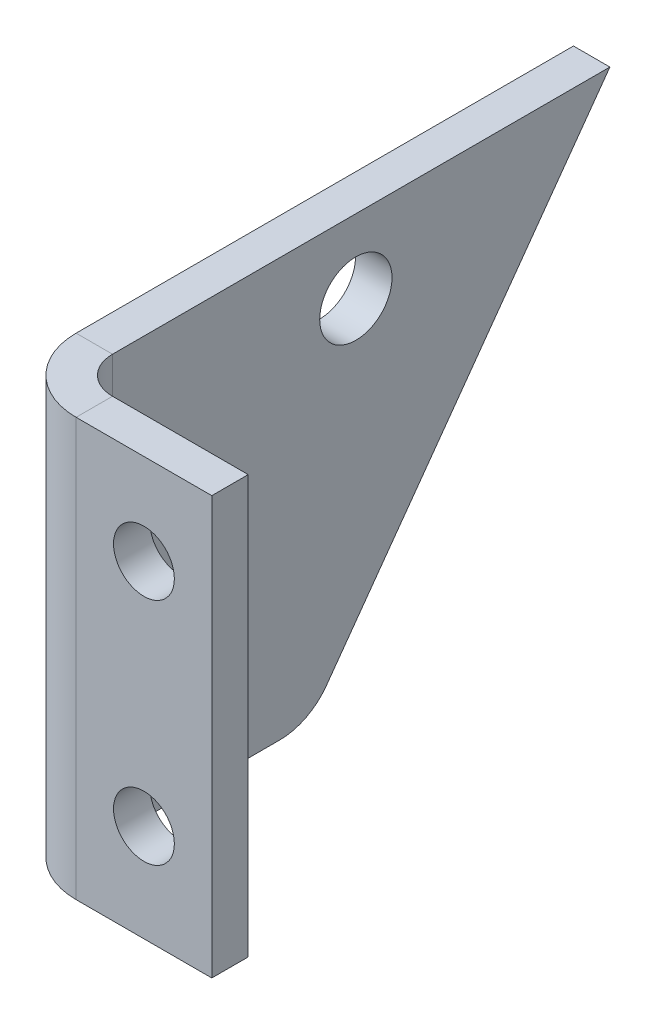
SolidWorks part; units mm, degrees
note: The reader was unsure of these and kept them because the rebuilt part matched: flange length of "Edge-Flange1".
ref_plane "Front Plane" through (0, 0, 0) normal (0, 0, 1) x (1, 0, 0)
ref_plane "Top Plane" through (0, 0, 0) normal (0, 1, 0) x (1, 0, 0)
ref_plane "Right Plane" through (0, 0, 0) normal (1, 0, 0) x (0, 0, -1)
sketch "Sketch1" plane through (0, 0, 0) normal (1, 0, 0) x (0, 0, -1)
  line B0 (15.5145, 80.4634) -> (48.2755, 80.6063)
  line B1 (53.2972, 75.6298) -> (53.4491, 43.2583)
  line B2 (0, 0) -> (0, 38.4283)
  line B3 (0, 38.4283) -> (-38.5, 38.5)
  line B4 (-38.5, 38.5) -> (-38.5, 49.4616)
  line B5 (-35.8424, 53.8789) -> (13.1939, 79.8808)
  line B6 (0, 0) -> (20.9311, 0)
  line B7 (24.9893, 2.0792) -> (52.5074, 40.3141)
  arc B8 (53.2972, 75.6298) -> (48.2755, 80.6063) centre (48.2973, 75.6063) ccw
  arc B9 (-38.5, 49.4616) -> (-35.8424, 53.8789) centre (-33.5, 49.4616) cw
  arc B10 (20.9311, 0) -> (24.9893, 2.0792) centre (20.9311, 5) ccw
  circle B11 centre (16.9387, 43.9655) radius 1.5
  ellipse B12 centre (47.9374, 44.1038) end of major axis (47.1974, 45.4086) minor radius 1.5
  spline B13 degree 3 poles (27.4588, 48.3261) (32.0962, 47.4253) (36.7252, 48.3676) (40.6413, 51.0097) (43.2482, 54.9493) (44.149, 59.5866) (43.2066, 64.2157) (40.5646, 68.1317) (36.625, 70.7386) (31.9877, 71.6394) (27.3586, 70.6971) (23.4426, 68.055) (20.8357, 64.1154) (19.9348, 59.4781) (20.8772, 54.8491) (23.5193, 50.933) (27.4588, 48.3261) (32.0962, 47.4253) (36.7252, 48.3676) knots -1.178097 -0.785398 -0.392699 0 0.392699 0.785398 1.178097 1.570796 1.963495 2.356194 2.748894 3.141593 3.534292 3.926991 4.31969 4.712389 5.105088 5.497787 5.890486 6.283185 6.675884 7.068583 7.461283 only from (32.0948, 47.7325) to (32.0948, 47.7325)
sketch_block_instance "motormount-1"
sketch_block "motormount" parameters "D1"=5
sketch "Sketch2" plane through (0, 0, 0) normal (1, 0, 0) x (0, 0, -1)
  line L0 (0, 0) -> (0, 38.4283) construction
  line L1 (0, 0) -> (20.9311, 0) construction
  line L2 (24.9893, 2.0792) -> (52.5074, 40.3141) construction
  line L3 (0, 0) -> (0, 36.404)
  line L4 (0, 0) -> (20.9311, 0)
  line L5 (24.9893, 2.0792) -> (49.6932, 36.404)
  line L6 (0, 36.404) -> (49.6932, 36.404)
  arc A0 (20.9311, 0) -> (24.9893, 2.0792) centre (20.9311, 5) ccw construction
  arc A1 (20.9311, 0) -> (24.9893, 2.0792) centre (20.9311, 5) ccw
base flange "Base-Flange1" sketch "Sketch2" thickness 3.175 reverse thickness direction no parameters "D1"=3.175
sketch "Sketch7" plane through (-3.175, 0, 0) normal (-1, 0, 0) x (0, 0, 1)
  line L0 (0, 0) -> (0, 10) construction
  line L1 (0, 0) -> (0, 38.4283) construction
  line L2 (-12.5877, 6.85) -> (-12.5877, 13.15) construction
  line L3 (0, 10) -> (0, 30.7947) construction
  line L4 (-26.1531, 27.1786) -> (-28.9547, 32.8214) construction
  line L5 (0, 10) -> (-30.69, 10)
  line L6 (-24.9893, 2.0792) -> (-52.5074, 40.3141) construction
  line L10 (-24.9893, 2.0792) -> (-49.6932, 36.404) construction
  line L11 (-24.9893, 2.0792) -> (-49.6932, 36.404)
  circle A0 centre (-27.5539, 30) radius 3.15
  circle A1 centre (-12.5877, 10) radius 3.15
  point P9 (-12.5877, 10)
  point P15 (-22.5421, 30)
  dimension "D3" = 6.3
  dimension "D4" = 6.3
  dimension "D1" = 10
  dimension "D2" = 20
extrude "Cut-Extrude3" cut sketch "Sketch7" against normal blind 10 contours A0 | A1 normal cut yes
edge flange "Edge-Flange1" sketch "Sketch11" flange angle 90 flange length 15 flange position material inside bend radius 3.175 thickness 3.175 relief rectangular parameters "D6"=10
sketch "Sketch11" plane through (0, 0, 0) normal (0, 0, -1) x (0, 1, 0)
  line L0 (36.404, 0) -> (0, 0) construction
  line L2 (0, 0) -> (0, 15)
  line L3 (0, 15) -> (36.404, 15)
  line L4 (36.404, 15) -> (36.404, 0)
  line L5 (36.404, 0) -> (0, 0)
bend "EdgeBend1" bend radius 3.175 bend angle 90 parameters "D5"=1
sketch "Sketch12" plane through (0, 0, -3.175) normal (0, 0, -1) x (-1, 0, 0)
  line L0 (-9.0875, 36.404) -> (-9.0875, -2.0794) construction
  line L1 (-3.175, 36.404) -> (-15, 36.404) construction
  circle A0 centre (-9.0875, 28.4964) radius 2.65
  circle A1 centre (-9.0875, 8.4966) radius 2.65
  line B0 (-29.9951, 80.363) -> (-29.9958, 74.363)
  line B1 (-29.9958, 74.363) -> (-9.9958, 74.3607)
  line B2 (-9.9958, 74.3607) -> (-9.9951, 80.3607)
  line B3 (-9.9951, 80.3607) -> (-29.9951, 80.363)
  line B4 (-39.9997, 41.3642) -> (-40, 38.3642)
  line B5 (-40, 38.3642) -> (-30, 38.363)
  line B6 (-30, 38.363) -> (-29.9997, 41.363)
  line B7 (-10, 38.3607) -> (0, 38.3596)
  line B8 (0, 38.3596) -> (0.0003, 41.3596)
  line B9 (-9.9997, 41.3607) -> (-10, 38.3607)
  line B10 (-29.9993, 44.363) -> (-30, 38.363)
  line B11 (-30, 38.363) -> (-10, 38.3607)
  line B12 (-10, 38.3607) -> (-9.9993, 44.3607)
  line B13 (0.0003, 41.3596) -> (0.0045, 77.3596)
  line B14 (-9.9955, 77.3607) -> (-9.9958, 74.3607)
  line B15 (-9.9958, 74.3607) -> (-29.9958, 74.363)
  line B16 (-29.9958, 74.363) -> (-29.9955, 77.363)
  line B17 (-39.9955, 77.3642) -> (-39.9997, 41.3642)
  line B18 (-29.9997, 41.363) -> (-29.9993, 44.363)
  line B19 (-9.9993, 44.3607) -> (-9.9997, 41.3607)
  line B20 (-29.9951, 80.363) -> (-39.9951, 80.3642)
  line B21 (-39.9951, 80.3642) -> (-39.9955, 77.3642)
  line B22 (-29.9955, 77.363) -> (-29.9951, 80.363)
  line B23 (0.0045, 77.3596) -> (0.0049, 80.3596)
  line B24 (0.0049, 80.3596) -> (-9.9951, 80.3607)
  line B25 (-9.9951, 80.3607) -> (-9.9955, 77.3607)
  line B26 (380.7227, 28.4513) -> (-19.2773, 28.4976)
  line B27 (380.7203, 8.4515) -> (-19.2797, 8.4978)
  line B28 (380.7194, -0.0771) -> (-19.2806, -0.0308)
  line B29 (380.7236, 36.9226) -> (-19.2764, 36.9688)
  dimension "D1" = 5.3
  dimension "D2" = 5.3
sketch_block_instance "motormount_back-1"
sketch_block "motormount_back" parameters "D1"=5.4262, "D2"=5.7071
extrude "Cut-Extrude4" cut sketch "Sketch12" against normal blind 10 contours L0 A0 B26 | A0 L0 B26 | A1
sketch "Bend-Lines1" [suppressed] plane through (0, 0, 0) normal (0, 1, 0) x (1, 0, 0)
sketch "Bounding-Box1" [suppressed] plane through (0, 0, 0) normal (0, 1, 0) x (1, 0, 0)
sheet metal parameters "Sheet-Metal1" thickness 3.175 parameters "D1"=3.175
flat pattern "Flat-Pattern1" [suppressed]
sketch "Bend-Lines2" plane through (0, 0, 0) normal (0, 1, 0) x (1, 0, 0)
sketch3d "Bounding-Box2" [suppressed]
  line L0 (-20.9311, -5, 0) -> (28.7622, -5, 0) construction
  line L1 (-20.9311, 31.404, 0) -> (28.7622, 31.404, 0) construction
  line L2 (-20.9311, -5, 0) -> (-20.9311, 31.404, 0) construction
  line L3 (28.7622, -5, 0) -> (28.7622, 31.404, 0) construction
sketch "Sketch7-1" [suppressed] plane through (-3.175, 0, 0) normal (-1, 0, 0) x (0, 0, 1)
  line L0 (0, 0) -> (0, 9.9338) construction
  line L2 (-12.54, 6.7838) -> (-12.54, 13.0838) construction
  line L3 (0, 9.9338) -> (0, 30.7947) construction
  line L4 (-26.1531, 27.9733) -> (-28.9547, 33.6161) construction
  line L5 (0, 9.9338) -> (-30.6423, 9.9338)
  line L7 (0, 30.7947) -> (-45.6562, 30.7947)
  line L9 (-12.54, 9.9338) -> (-32.2907, 37.3762)
  line L11 (-24.9893, 2.0792) -> (-49.6932, 36.404)
  circle A0 centre (-27.5539, 30.7947) radius 3.15
  circle A1 centre (-12.54, 9.9338) radius 3.15
  point P9 (-12.54, 9.9338)
  point P15 (-22.5421, 30)
sheet metal parameters "Sheet-Metal4" thickness 3.175 parameters "D1"=3.175
flat pattern "Flat-Pattern1" [suppressed]
sketch "Bend-Lines2" plane through (0, 0, 0) normal (0, 1, 0) x (1, 0, 0)
sketch3d "Bounding-Box2" [suppressed]
  line L0 (-20.9311, -5, 0) -> (28.7622, -5, 0) construction
  line L1 (-20.9311, 31.404, 0) -> (28.7622, 31.404, 0) construction
  line L2 (-20.9311, -5, 0) -> (-20.9311, 31.404, 0) construction
  line L3 (28.7622, -5, 0) -> (28.7622, 31.404, 0) construction
sketch "Sketch7-1" [suppressed] plane through (-3.175, 0, 0) normal (-1, 0, 0) x (0, 0, 1)
  line L0 (0, 0) -> (0, 10) construction
  line L2 (-12.5877, 6.85) -> (-12.5877, 13.15) construction
  line L3 (0, 10) -> (0, 30.7947) construction
  line L4 (-26.1531, 27.1786) -> (-28.9547, 32.8214) construction
  line L5 (0, 10) -> (-30.69, 10)
  line L11 (-24.9893, 2.0792) -> (-49.6932, 36.404)
  circle A0 centre (-27.5539, 30) radius 3.15
  circle A1 centre (-12.5877, 10) radius 3.15
  point P9 (-12.5877, 10)
  point P15 (-22.5421, 30)
  dimension "D1" = 10
  dimension "D2" = 20
sheet metal parameters "Sheet-Metal5" thickness 3.175 parameters "D1"=3.175
flat pattern "Flat-Pattern1"
sketch "Bend-Lines2" plane through (0, 0, 0) normal (1, 0, 0) x (0, 0, -1)
  line L0 (2.7592, 36.404) -> (2.7592, 0) construction
  line L1 (2.7592, 36.404) -> (2.7592, 0) construction
sketch3d "Bounding-Box2" [suppressed]
  line L0 (-33.5878, -5, 0) -> (28.7622, -5, 0) construction
  line L1 (-33.5878, 31.404, 0) -> (28.7622, 31.404, 0) construction
  line L2 (-33.5878, -5, 0) -> (-33.5878, 31.404, 0) construction
  line L3 (28.7622, -5, 0) -> (28.7622, 31.404, 0) construction
bend of the flat pattern "Flatten-<EdgeBend1>1"
sheet metal parameters "Sheet-Metal6" thickness 3.175 parameters "D1"=3.175
flat pattern "Flat-Pattern1"
sketch "Bend-Lines2" plane through (0, 0, 0) normal (1, 0, 0) x (0, 0, -1)
  line L0 (2.7592, 36.404) -> (2.7592, 0) construction
  line L1 (2.7592, 36.404) -> (2.7592, 0) construction
sketch3d "Bounding-Box2" [suppressed]
  line L0 (-33.5878, -5, 0) -> (28.7622, -5, 0) construction
  line L1 (-33.5878, 31.404, 0) -> (28.7622, 31.404, 0) construction
  line L2 (-33.5878, -5, 0) -> (-33.5878, 31.404, 0) construction
  line L3 (28.7622, -5, 0) -> (28.7622, 31.404, 0) construction
bend of the flat pattern "Flatten-<EdgeBend1>1"
